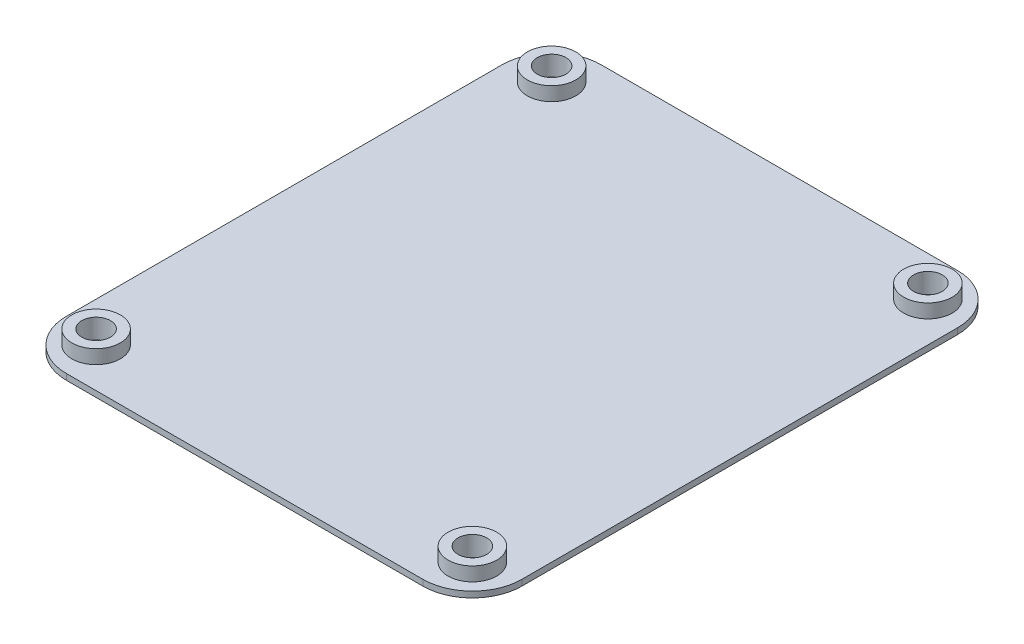
SolidWorks part; units mm, degrees
ref_plane "Front Plane" through (0, 0, 0) normal (0, 0, 1) x (1, 0, 0)
ref_plane "Top Plane" through (0, 0, 0) normal (0, 1, 0) x (1, 0, 0)
ref_plane "Right Plane" through (0, 0, 0) normal (1, 0, 0) x (0, 0, -1)
sketch "Sketch1" plane through (0, 0, 0) normal (0, 1, 0) x (1, 0, 0)
  line L0 (-23, 27) -> (23, 27)
  line L1 (-19, 23) -> (19, 23) construction
  line L2 (-19, 23) -> (-19, -23) construction
  line L3 (-19, -23) -> (19, -23) construction
  line L4 (19, 23) -> (19, -23) construction
  line L5 (23, 27) -> (23, -27)
  line L6 (-23, -27) -> (23, -27)
  line L7 (-23, 27) -> (-23, -27)
  circle A0 centre (-19, 23) radius 1.45
  circle A1 centre (19, 23) radius 1.45
  circle A2 centre (19, -23) radius 1.45
  circle A3 centre (-19, -23) radius 1.45
  circle A4 centre (-19, 23) radius 2.45
  circle A5 centre (19, 23) radius 2.45
  circle A6 centre (-19, -23) radius 2.45
  circle A7 centre (19, -23) radius 2.45
  point P4 (-19, 0)
  point P6 (0, 23)
  dimension "D4" = 2.9
  dimension "D1" = 38
  dimension "D2" = 46
  dimension "D3" = 4
  dimension "D5" = 1
extrude "Boss-Extrude1" add sketch "Sketch1" along normal blind 0.6 contours L0 L7 L6 L5 A7 A6 A5 A4 | A4 A0 | A5 A1 | A6 A3 | A7 A2 region at (0, 0, 0) region at (-21.3807, 0, -23) region at (16.6193, 0, -23) region at (-21.3807, 0, 23) region at (16.6193, 0, 23)
extrude "Boss-Extrude2" add sketch "Sketch1<3>" along normal blind 2 contours A6 A3 | A7 A2 | A4 A0 | A5 A1 region at (-21.3807, 0, -23) region at (16.6193, 0, -23) region at (-21.3807, 0, 23) region at (16.6193, 0, 23)
sketch "Sketch1<3>" plane through (0, 0, 0) normal (0, 1, 0) x (1, 0, 0) same geometry as "Sketch1"
fillet "Fillet1" radius 5 4 edges at (-23, 0.3, -27) (23, 0.3, -27) (-23, 0.3, 27) (23, 0.3, 27)
